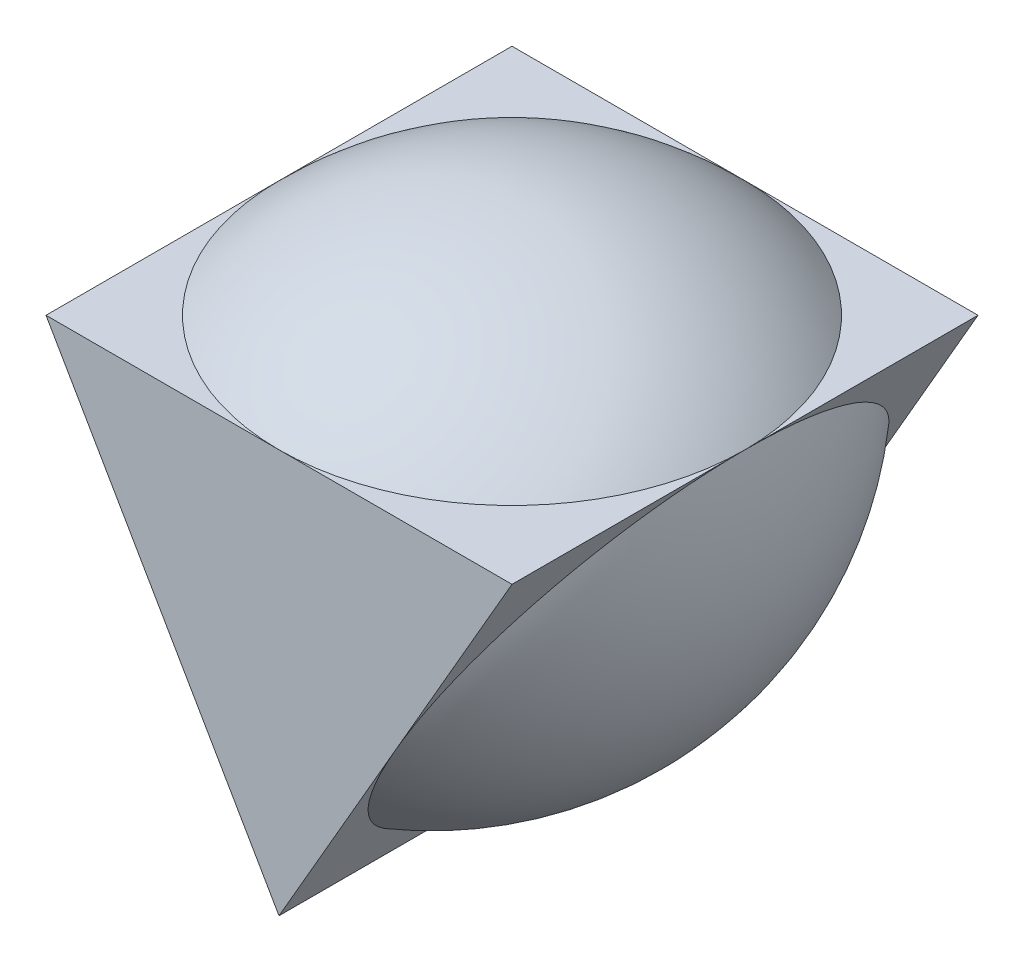
SolidWorks part; units mm, degrees
ref_plane "Front Plane" through (0, 0, 0) normal (0, 0, 1) x (1, 0, 0)
ref_plane "Top Plane" through (0, 0, 0) normal (0, 1, 0) x (1, 0, 0)
ref_plane "Right Plane" through (0, 0, 0) normal (1, 0, 0) x (0, 0, -1)
sketch "Sketch2" plane through (0, 0, 0) normal (0, 0, 1) x (1, 0, 0)
  line L0 (0, 0) -> (0, -11.547) construction
  line L1 (0, 0) -> (-10, 5.7735) construction
  line L2 (0, 0) -> (10, 5.7735) construction
  line L3 (0, 0) -> (0, -4) construction
  line L4 (-10, 5.7735) -> (10, 5.7735)
  line L5 (0, -11.547) -> (10, 5.7735)
  line L6 (-10, 5.7735) -> (0, -11.547)
  line L7 (0, 0) -> (5, -2.8868) construction
  line L8 (0, 0) -> (0, 9.9829) construction
  line L9 (0, 9.9829) -> (0, 5.7735)
  line L10 (0, 5.7735) -> (10, 5.7735)
  arc A3 (10, 5.7735) -> (0, 9.9829) centre (0, -4) ccw
  point P8 (0, 0)
  point P16 (0, 0)
  dimension "D2" = 20
  dimension "D3" = 4
  dimension "D1" = 3
extrude "Boss-Extrude1" add sketch "Sketch2" along normal blind 10 and the other way blind 10 contours L4 L6 L5 region at (0, 0, 0)
sketch "Sketch3" plane through (5, -2.8868, 0) normal (0.866, -0.5, 0) x (0, 0, -1)
  arc A1 (10, 0) -> (0, -10) centre (0, 0) cw
sketch "Sketch4" plane through (-5, -2.8868, 0) normal (-0.866, -0.5, 0) x (0, 0, 1)
  arc A0 (0, -9.8989) -> (-9.8989, 0) centre (0, 0) cw
sketch "Sketch5" plane through (0, 0, -10) normal (0, 0, -1) x (-1, 0, 0)
  line L0 (10, 5.7735) -> (0, -11.547) construction
  line L1 (0, -11.547) -> (-10, 5.7735) construction
  arc A0 (5, -2.8868) -> (-5, -2.8868) centre (0, 0) cw
revolve "Revolve3" add sketch "Sketch2<7>" angle 360 about L9 region at (3.8387, 7.4811, 0)
sketch "Sketch2<7>" plane through (0, 0, 0) normal (0, 0, 1) x (1, 0, 0) same geometry as "Sketch2"
pattern_circular "CirPattern1" count 3 every 120 about axis through (0, 0, -10) along (0, 0, -1) of "Revolve3"
